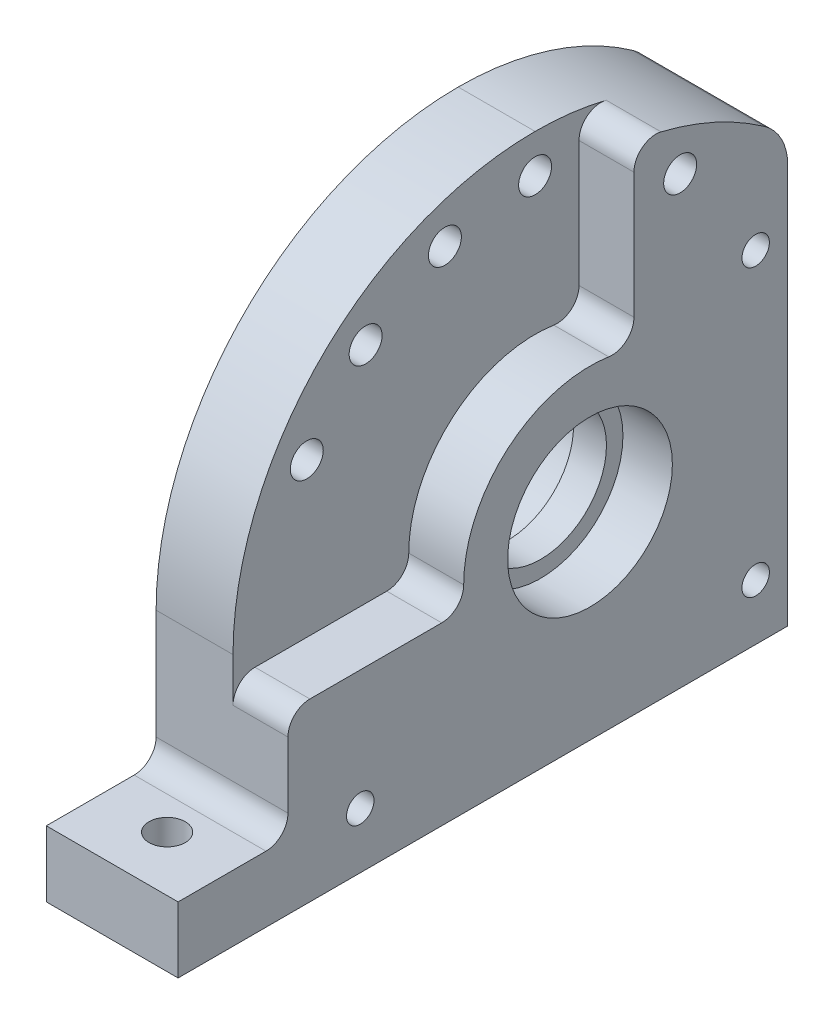
SolidWorks part; units mm, degrees
material "A5052"
ref_plane "Front Plane" through (0, 0, 0) normal (0, 0, 1) x (1, 0, 0)
ref_plane "Top Plane" through (0, 0, 0) normal (0, 1, 0) x (1, 0, 0)
ref_plane "Right Plane" through (0, 0, 0) normal (1, 0, 0) x (0, 0, -1)
sketch "Sketch1" plane through (0, 0, 0) normal (1, 0, 0) x (0, 0, -1)
  line L1 (-27.5, 22.75) -> (27.5, 22.75)
  line L2 (-27.5, 22.75) -> (-27.5, -22.75)
  line L3 (-27.5, -22.75) -> (27.5, -22.75)
  line L4 (27.5, 22.75) -> (27.5, -22.75)
  line L5 (-27.5, 22.75) -> (27.5, -22.75) construction
  line L6 (-27.5, -22.75) -> (27.5, 22.75) construction
  point P0 (0, 0)
  dimension "D1" = 55
  dimension "D2" = 45.5
extrude "Boss-Extrude1" add sketch "Sketch1" along normal mid plane 12
fillet "Fillet1" radius 27.5 2 edges at (0, 22.75, -27.5) (0, 22.75, 27.5)
sketch "Sketch2" plane through (0, 0, 0) normal (1, 0, 0) x (0, 0, -1)
  line L0 (-27.5, -22.75) -> (27.5, -22.75) construction
  line L1 (-37.5, -16.75) -> (37.5, -16.75)
  line L2 (-37.5, -16.75) -> (-37.5, -22.75)
  line L3 (-37.5, -22.75) -> (37.5, -22.75)
  line L4 (37.5, -16.75) -> (37.5, -22.75)
  line L5 (-37.5, -16.75) -> (37.5, -22.75) construction
  line L6 (-37.5, -22.75) -> (37.5, -16.75) construction
  line L7 (0, -19.75) -> (0, 0) construction
  point P0 (0, -19.75)
  dimension "D1" = 6
  dimension "D2" = 75
extrude "Boss-Extrude2" add sketch "Sketch2" along normal mid plane 12
fillet "Fillet2" radius 2 2 edges at (0, -16.75, -27.5) (0, -16.75, 27.5)
sketch "Sketch5" plane through (-6, 0, 0) normal (1, 0, 0) x (0, 0, -1)
  line L0 (0, -4.75) -> (0, 19.25) construction
  line L1 (0, -4.75) -> (-8.2085, 17.8026) construction
  line L2 (0, -4.75) -> (-15.4269, 13.6351) construction
  line L3 (0, -4.75) -> (8.2085, 17.8026) construction
  line L4 (0, -4.75) -> (16.9706, 12.2206) construction
  line L5 (0, -4.75) -> (-20.7846, 7.25) construction
  line L6 (0, -4.75) -> (22.5526, 3.4585) construction
  circle A0 centre (0, 19.25) radius 3
  circle A1 centre (0, -4.75) radius 24 construction
  circle A3 centre (-8.2085, 17.8026) radius 3
  circle A4 centre (-15.4269, 13.6351) radius 3
  circle A5 centre (8.2085, 17.8026) radius 3
  circle A6 centre (16.9706, 12.2206) radius 3
  circle A7 centre (22.5526, 3.4585) radius 3
  circle A8 centre (-20.7846, 7.25) radius 3
  dimension "D1" = 6
  dimension "D2" = 48
  dimension "D3" = 20
  dimension "D4" = 20
  dimension "D5" = 20
  dimension "D6" = 25
  dimension "D7" = 20
  dimension "D8" = 25
extrude "Cut-Extrude1" cut sketch "Sketch5" along normal blind 4
sketch "Sketch6" plane through (-6, 0, 0) normal (-1, 0, 0) x (0, 0, 1)
  circle A0 centre (0, -4.75) radius 7.5
  dimension "D1" = 15
extrude "Cut-Extrude2" cut sketch "Sketch6" against normal blind 4.5
sketch "Sketch17" plane through (6, 0, 0) normal (1, 0, 0) x (0, 0, -1)
  circle A1 centre (0, -4.75) radius 7.5
  circle A2 centre (0, -4.75) radius 7.5
  dimension "D1" = 0
extrude "Cut-Extrude7" cut sketch "Sketch17" against normal blind 4.5
sketch "Sketch7" plane through (-6, 0, 0) normal (-1, 0, 0) x (0, 0, 1)
  circle A0 centre (0, -4.75) radius 6
  dimension "D1" = 12
extrude "Cut-Extrude3" cut sketch "Sketch7" against normal through all
sketch "Sketch8" plane through (6, 0, 0) normal (1, 0, 0) x (0, 0, -1)
  line L0 (18, 34.4359) -> (18, -16.75)
  line L1 (18, 34.4359) -> (37.5, 34.4359)
  line L2 (37.5, 34.4359) -> (37.5, -16.75)
  line L3 (37.5, -16.75) -> (18, -16.75)
  dimension "D1" = 18
extrude "Cut-Extrude4" cut sketch "Sketch8" against normal through all
fillet "Fillet4" radius 5 1 edges at (0, 16.0406, -18)
hole_wizard "M3x0.5 Tapped Hole1" positions "Sketch10" profile "Sketch11" tap size "M3x0.5" standard "ANSI Metric" end condition through all
sketch "Sketch10" plane through (-6, 0, 0) normal (-1, 0, 0) x (0, 0, 1)
  point P16 (20.9169, -17.6638)
  point P67 (-15.0831, 8.3362)
  point P68 (-15.0831, -17.6638)
sketch "Sketch11" plane through (-6, -17.6638, 20.9169) normal (0, 1, 0) x (0, 0, 1)
  line L0 (0, 0) -> (0, 12)
  line L1 (0, 12) -> (1.25, 12)
  line L2 (1.25, 12) -> (1.25, 0)
  line L5 (1.25, 0) -> (0, 0)
  line L11 (0, -6.35) -> (0, 107.95) construction
  dimension "Thru Tap Drill Dia." = 2.5
  dimension "Thru Tap Drill Depth" = 12
cosmetic thread "Hole Thread2" parameters "D2"=3
cosmetic thread "Hole Thread3" parameters "D2"=3
cosmetic thread "Hole Thread4" parameters "D2"=3
sketch "Sketch12" plane through (6, 0, 0) normal (1, 0, 0) x (0, 0, -1)
  circle A0 centre (-20.7846, 7.25) radius 1.5
  circle A1 centre (-15.4269, 13.6351) radius 1.5
  circle A2 centre (-8.2085, 17.8026) radius 1.5
  circle A3 centre (0, 19.25) radius 1.5
  circle A4 centre (8.2085, 17.8026) radius 1.5
  dimension "D1" = 3
extrude "Cut-Extrude6" cut sketch "Sketch12" against normal through all
sketch "Sketch13" plane through (-2, 0, 0) normal (-1, 0, 0) x (0, 0, 1)
  line L1 (-18, 13.6144) -> (-18, 9.4027)
  line L5 (-18, 13.6144) -> (-18, 9.4027)
  arc A1 (-18, 9.4027) -> (-17.7705, 15.112) centre (-16.9706, 12.2206) ccw
  arc A2 (-18, 9.4027) -> (-17.7705, 15.112) centre (-16.9706, 12.2206) ccw
  arc A4 (-17.7705, 15.112) -> (-18, 13.6144) centre (-13, 13.6144) ccw
  arc A5 (-17.7705, 15.112) -> (-18, 13.6144) centre (-13, 13.6144) ccw
  dimension "D1" = 0
extrude "Boss-Extrude3" add sketch "Sketch13" along normal up to surface (-8 mm away) up to face at (6, 7.25, 19.2846)
sketch "Sketch15" plane through (-2, 0, 0) normal (-1, 0, 0) x (0, 0, 1)
  line L1 (-18, 13.6144) -> (-18, 9.4027)
  line L2 (-18, 13.6144) -> (-18, 9.4027)
  arc A1 (-18, 9.4027) -> (-17.7705, 15.112) centre (-16.9706, 12.2206) ccw
  arc A2 (-18, 9.4027) -> (-17.7705, 15.112) centre (-16.9706, 12.2206) ccw
  arc A4 (-17.7705, 15.112) -> (-18, 13.6144) centre (-13, 13.6144) ccw
  arc A5 (-17.7705, 15.112) -> (-18, 13.6144) centre (-13, 13.6144) ccw
  dimension "D1" = 0
extrude "Boss-Extrude4" add sketch "Sketch15" along normal up to surface (4 mm away) up to face at (-6, -17.6638, 22.1669)
sketch "Sketch18" plane through (6, 0, 0) normal (1, 0, 0) x (0, 0, -1)
  line L0 (-32.4945, -6.75) -> (-11.3248, -6.75)
  line L2 (4, 6.0319) -> (4, 24.3064)
  line L3 (4, 24.3064) -> (-32.4945, 24.3064)
  line L4 (-32.4945, 24.3064) -> (-32.4945, -6.75)
  line L5 (18, 13.6144) -> (18, -16.75) construction
  line L6 (-37.5, -22.75) -> (37.5, -22.75) construction
  arc A0 (4, 6.0319) -> (-11.3248, -6.75) centre (0, -4.75) ccw
  dimension "D5" = 23
  dimension "D2" = 14
  dimension "D3" = 16
extrude "Cut-Extrude8" cut sketch "Sketch18" against normal blind 5
fillet "Fillet5" radius 2 2 edges at (3.5, -6.75, 11.3248) (3.5, 6.0319, -4)
fillet "Fillet6" radius 2 2 edges at (3.5, -6.75, 27.5) (3.5, 22.4575, -4)
sketch "Sketch19" plane through (0, -16.75, 0) normal (0, 1, 0) x (1, 0, 0)
  line L4 (-6, 37.5) -> (-6, 18)
  line L5 (-6, 18) -> (6, 18)
  line L6 (6, 18) -> (6, 37.5)
  line L7 (6, 37.5) -> (-6, 37.5)
  line L8 (-6, 37.5) -> (-6, 18)
  line L9 (-6, 18) -> (6, 18)
  line L10 (6, 18) -> (6, 37.5)
  line L11 (6, 37.5) -> (-6, 37.5)
  dimension "D1" = 0
extrude "Cut-Extrude9" cut sketch "Sketch19" against normal through all
hole_wizard "M4x0.7 Tapped Hole1" positions "Sketch20" profile "Sketch21" tap size "M4x0.7" standard "ANSI Metric" end condition through all
sketch "Sketch20" plane through (0, -22.75, 0) normal (0, -1, 0) x (-1, 0, 0)
  line L0 (0, 0) -> (0, -32.5) construction
  line L2 (-6, -37.5) -> (6, -37.5) construction
  point P0 (0, -32.5)
  dimension "D1" = 5
sketch "Sketch21" plane through (0, -22.75, 32.5) normal (1, 0, 0) x (0, 0, -1)
  line L0 (0, 0) -> (0, 45.5)
  line L1 (0, 45.5) -> (1.65, 45.5)
  line L2 (1.65, 45.5) -> (1.65, 0)
  line L5 (1.65, 0) -> (0, 0)
  line L11 (0, -6.35) -> (0, 107.95) construction
  dimension "Thru Tap Drill Dia." = 3.3
  dimension "Thru Tap Drill Depth" = 45.5
cosmetic thread "Hole Thread5" parameters "D2"=4
hole_wizard "M4x0.7 Tapped Hole2" positions "Sketch22" profile "Sketch24" tap size "M4x0.7" standard "ANSI Metric"
sketch "Sketch22" plane through (0, -22.75, 0) normal (0, -1, 0) x (-1, 0, 0)
  line L0 (0, 18) -> (0, 10) construction
  line L1 (6, 18) -> (-6, 18) construction
  point P0 (0, 10)
  dimension "D1" = 8
sketch "Sketch24" plane through (0, -22.75, -10) normal (1, 0, 0) x (0, 0, -1)
  line L0 (0, 0) -> (0, 9.0914)
  line L1 (0, 9.0914) -> (1.65, 8.1)
  line L2 (1.65, 8.1) -> (1.65, 0)
  line L5 (1.65, 0) -> (0, 0)
  line L10 (0, 9.0914) -> (-1.65, 8.1) construction
  line L11 (0, -6.35) -> (0, 107.95) construction
  dimension "Tap Drill Dia." = 3.3
  dimension "Tap Drill Depth" = 8.1
  dimension "Drill Angle" = 118
cosmetic thread "Hole Thread6" parameters "D1"=6, "D2"=4
